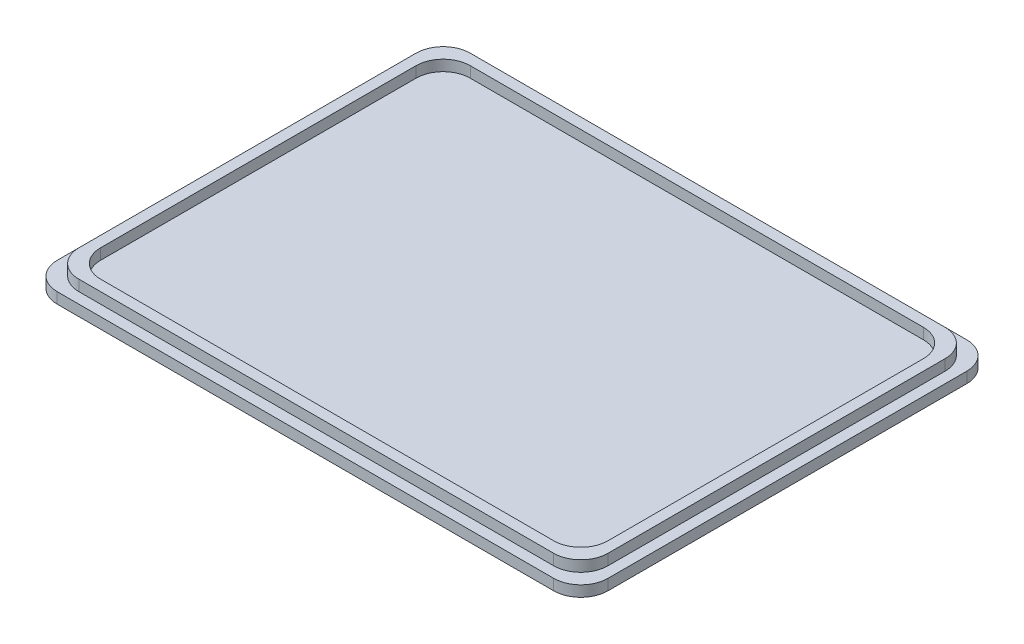
SolidWorks part; units mm, degrees
ref_plane "Front Plane" through (0, 0, 0) normal (0, 0, 1) x (1, 0, 0)
ref_plane "Top Plane" through (0, 0, 0) normal (0, 1, 0) x (1, 0, 0)
ref_plane "Right Plane" through (0, 0, 0) normal (1, 0, 0) x (0, 0, -1)
sketch "Sketch1" plane through (0, 0, 0) normal (0, 1, 0) x (1, 0, 0)
  line L1 (-50.8, -38.1) -> (50.8, -38.1)
  line L2 (-50.8, -38.1) -> (-50.8, 38.1)
  line L3 (-50.8, 38.1) -> (50.8, 38.1)
  line L4 (50.8, -38.1) -> (50.8, 38.1)
  line L5 (-50.8, -38.1) -> (50.8, 38.1) construction
  line L6 (-50.8, 38.1) -> (50.8, -38.1) construction
  point P0 (0, 0)
extrude "Boss-Extrude1" add sketch "Sketch1" along normal blind 2
sketch "Sketch2" plane through (0, 2, 0) normal (0, 1, 0) x (1, 0, 0)
  line L0 (-50.8, -38.1) -> (50.8, -38.1) construction
  line L1 (50.8, -38.1) -> (50.8, 38.1) construction
  line L2 (50.8, 38.1) -> (-50.8, 38.1) construction
  line L3 (-50.8, 38.1) -> (-50.8, -38.1) construction
  line L4 (-48.8, 36.1) -> (-48.8, -36.1)
  line L5 (-48.8, -36.1) -> (48.8, -36.1)
  line L6 (48.8, -36.1) -> (48.8, 36.1)
  line L7 (48.8, 36.1) -> (-48.8, 36.1)
  line L8 (-46.8, 34.1) -> (-46.8, -34.1)
  line L9 (-46.8, -34.1) -> (46.8, -34.1)
  line L10 (46.8, -34.1) -> (46.8, 34.1)
  line L11 (46.8, 34.1) -> (-46.8, 34.1)
  dimension "D1" = 2
  dimension "D2" = 2
extrude "Extrude-Thin1" add sketch "Sketch2" along normal blind 2 thin contours L4 L5 L6 L7 thin type one direction reverse wall 2
fillet "Fillet1" radius 5 4 edges at (-50.8, 1, -38.1) (-50.8, 1, 38.1) (50.8, 1, -38.1) (50.8, 1, 38.1)
fillet "Fillet2" radius 5 8 edges at (46.8, 3, -34.1) (46.8, 3, 34.1) (-46.8, 3, 34.1) (-46.8, 3, -34.1) (48.8, 3, -36.1) (48.8, 3, 36.1) (-48.8, 3, 36.1) (-48.8, 3, -36.1)
sketch "Sketch3" plane through (0, 0, 0) normal (0, -1, 0) x (1, 0, 0)
  text T0 "ΔΣ\r\n" font "Century Gothic" height in points 48
extrude "Cut-Extrude1" cut sketch "Sketch3" against normal blind 1
